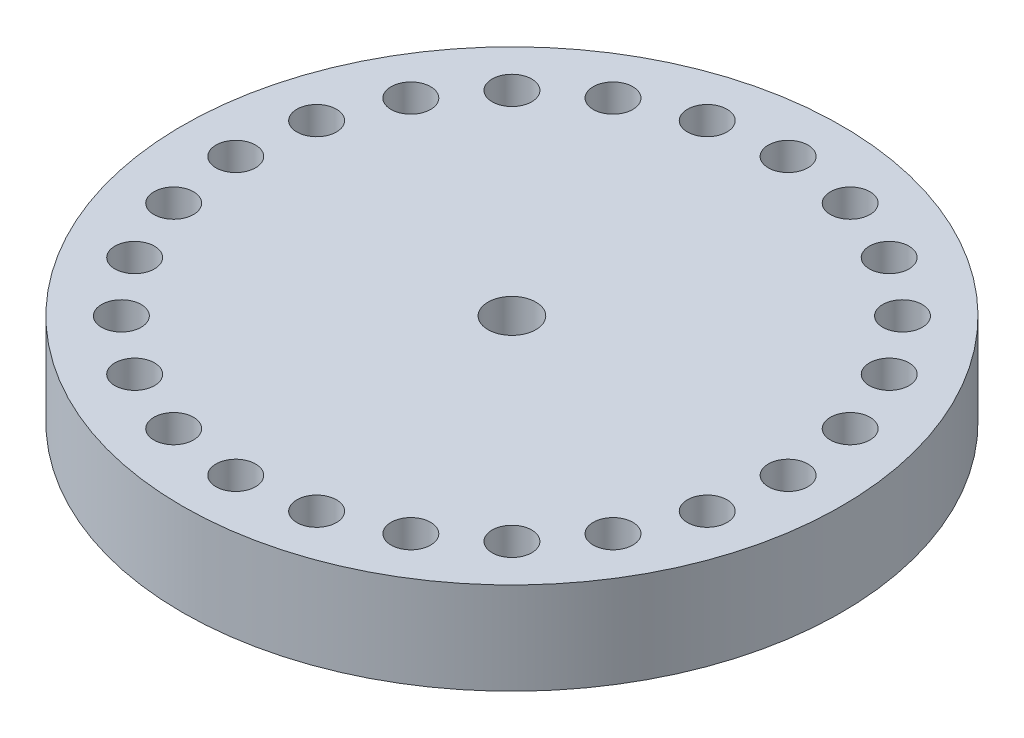
SolidWorks part; units mm, degrees
ref_plane "Front Plane" through (0, 0, 0) normal (0, 0, 1) x (1, 0, 0)
ref_plane "Top Plane" through (0, 0, 0) normal (0, 1, 0) x (1, 0, 0)
ref_plane "Right Plane" through (0, 0, 0) normal (1, 0, 0) x (0, 0, -1)
sketch "Sketch1" plane through (0, 0, 0) normal (0, 1, 0) x (1, 0, 0)
  circle A0 centre (0, 0) radius 20.066 construction
  circle A1 centre (0, 0) radius 45.466
  dimension "D1" = 25.4
extrude "Boss-Extrude1" add sketch "Sketch1" along normal blind 25.4
sketch "Sketch3" plane through (0, 0, 0) normal (0, -1, 0) x (1, 0, 0)
  circle A0 centre (0, 0) radius 19.05
  dimension "D1" = 38.1
sketch "Sketch4" plane through (0, 0, 0) normal (0, -1, 0) x (1, 0, 0)
  line L0 (0, 0) -> (0, 38.1) construction
  circle A0 centre (0, 38.1) radius 1.9812
  dimension "D1" = 38.1
  dimension "D2" = 3.9624
hole_wizard "CSK for 1/4 Flat Head Machine Screw1" positions "Sketch6" profile "Sketch7" countersink size "1/4" standard "ANSI Inch"
sketch "Sketch6" plane through (0, 25.4, 0) normal (0, 1, 0) x (1, 0, 0)
  point P0 (0, 0)
sketch "Sketch7" plane through (0, 25.4, 0) normal (1, 0, 0) x (0, 0, 1)
  line L0 (0, 0) -> (0, 27.3611)
  line L1 (0, 27.3611) -> (3.2639, 25.4)
  line L2 (3.2639, 25.4) -> (3.2639, 3.6524)
  line L3 (3.2639, 3.6524) -> (6.4389, 0)
  line L5 (6.4389, 0) -> (0, 0)
  line L6 (-3.2639, 3.6524) -> (-6.4389, 0) construction
  line L10 (0, 27.3611) -> (-3.2639, 25.4) construction
  line L11 (0, -6.35) -> (0, 107.95) construction
  dimension "Hole Dia." = 6.5278
  dimension "Hole Depth" = 25.4
  dimension "Near C'Sink Dia." = 12.8778
  dimension "Near C'Sink Angle" = 82
  dimension "Drill Angle" = 118
sketch "Sketch8" plane through (0, 25.4, 0) normal (0, 1, 0) x (1, 0, 0)
  circle A0 centre (0, 0) radius 46.9556
extrude "Cut-Extrude2" cut sketch "Sketch8" against normal blind 12.7
extrude "Cut-Extrude3" cut sketch "Sketch4" against normal through all
sketch "Sketch9" plane through (0, 12.7, 0) normal (0, 1, 0) x (1, 0, 0)
  circle A0 centre (0, -38.1) radius 2.7305
  dimension "D1" = 5.461
extrude "Cut-Extrude4" cut sketch "Sketch9" against normal blind 5.08
sketch "Sketch10" plane through (0, 12.7, 0) normal (0, 1, 0) x (1, 0, 0)
  circle A0 centre (0, 0) radius 22.8348
sketch "Sketch11" plane through (0, 12.7, 0) normal (0, 1, 0) x (1, 0, 0)
  circle A0 centre (0, 0) radius 3.302
  dimension "D1" = 6.604
extrude "Cut-Extrude5" cut sketch "Sketch11" against normal through all
pattern_circular "CirPattern2" count 24 every 15 about axis through (0, 12.7, 0) along (0, 1, 0) of "Cut-Extrude3"
sketch "Sketch12" plane through (0, 12.7, 0) normal (0, 1, 0) x (1, 0, 0)
  circle A0 centre (0, 0) radius 38.3099
pattern_circular "CirPattern3" count 24 every 15 about axis through (0, 12.7, 0) along (0, 1, 0) of "Cut-Extrude4"
ref_axis "Axis1" through (0, 0, 0) along (0, 1, 0)
ref_plane "Plane1" through (0, 0, 0) normal (1, 0, 0) x (0, 1, 0)
sketch "Sketch13" plane through (0, 0, 0) normal (1, 0, 0) x (0, 1, 0)
  line L0 (0, 0) -> (-14.1793, 0)
  line L1 (0, 0) -> (0, 19.05)
  line L2 (0, 19.05) -> (0, -19.05) construction
  line L3 (0, 19.05) -> (-13.4727, 2.2091)
  arc A0 (-13.4727, 2.2091) -> (-14.1793, 0) centre (-10.5569, 0.0589) ccw
revolve "Revolve1" add sketch "Sketch13" angle 360 about L0
